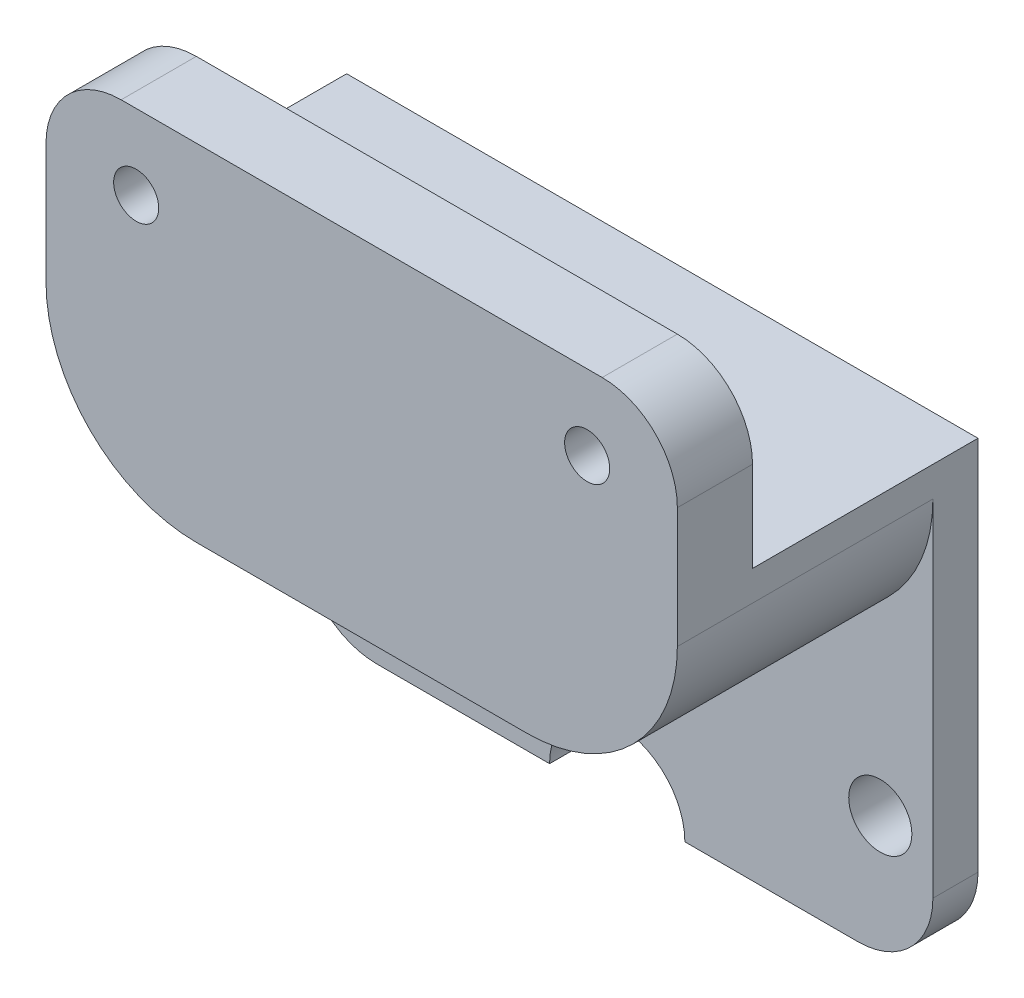
SolidWorks part; units mm, degrees
ref_plane "Front Plane" through (0, 0, 0) normal (0, 0, 1) x (1, 0, 0)
ref_plane "Top Plane" through (0, 0, 0) normal (0, 1, 0) x (1, 0, 0)
ref_plane "Right Plane" through (0, 0, 0) normal (1, 0, 0) x (0, 0, -1)
sketch "Sketch3" plane through (0, 0, 0) normal (0, 0, 1) x (1, 0, 0)
  line L0 (-22.5928, 16.5094) -> (-6.0928, 16.5094)
  line L1 (-48.0928, 16.5094) -> (-31.5928, 16.5094)
  line L2 (-48.0928, 16.5094) -> (-48.0928, 3.5094)
  line L3 (-38.0928, -6.4906) -> (-16.0928, -6.4906)
  line L4 (-6.0928, 16.5094) -> (-6.0928, 3.5094)
  line L5 (-31.5928, 16.5094) -> (-22.5928, 16.5094)
  circle A1 centre (-42.0928, 11.5094) radius 1.5
  circle A2 centre (-12.0928, 11.5094) radius 1.5
  arc A3 (-48.0928, 3.5094) -> (-38.0928, -6.4906) centre (-38.0928, 3.5094) ccw
  arc A4 (-16.0928, -6.4906) -> (-6.0928, 3.5094) centre (-16.0928, 3.5094) ccw
  point P12 (-27.0928, -6.4906)
  point P16 (-48.0928, -6.4906)
  dimension "D4" = 3
  dimension "D5" = 3
  dimension "D12" = 10
  dimension "D13" = 10
  dimension "D1" = 42
  dimension "D2" = 23
  dimension "D6" = 18
  dimension "D7" = 30
  dimension "D8" = 18
  dimension "D9" = 15
  dimension "D10" = 15
extrude "Boss-Extrude3" add sketch "Sketch3" along normal blind 5
sketch "Sketch6" plane through (0, 0, 0) normal (0, 0, 1) x (1, 0, 0)
  line L2 (-48.0928, 5.5094) -> (-48.0928, 3.5094)
  line L3 (-38.0928, -6.4906) -> (-16.0928, -6.4906)
  line L4 (-6.0928, 5.5094) -> (-6.0928, 3.5094)
  line L5 (-6.0928, 5.5094) -> (-48.0928, 5.5094)
  arc A3 (-48.0928, 3.5094) -> (-38.0928, -6.4906) centre (-38.0928, 3.5094) ccw
  arc A4 (-16.0928, -6.4906) -> (-6.0928, 3.5094) centre (-16.0928, 3.5094) ccw
  dimension "D1" = 12
extrude "Boss-Extrude4" add sketch "Sketch6" against normal blind 15
ref_plane "Plane7" through (0, 5.5094, 0) normal (0, 1, 0) x (1, 0, 0)
sketch "Sketch9" plane through (0, 5.5094, 0) normal (0, 1, 0) x (1, 0, 0)
  line L0 (-48.0928, 15) -> (-48.0928, 0) construction
  line L1 (-6.0928, 15) -> (-48.0928, 15)
  line L2 (-6.0928, 15) -> (-6.0928, 12)
  line L3 (-6.0928, 12) -> (-48.0928, 12)
  line L4 (-48.0928, 15) -> (-48.0928, 12)
  dimension "D1" = 42
  dimension "D2" = 3
fillet "Fillet4" radius 5 2 edges at (-48.0928, 16.5094, 2.5) (-6.0928, 16.5094, 2.5)
extrude "Boss-Extrude7" add sketch "Sketch9" against normal blind 30
fillet "Fillet6" radius 5 1 edges at (-6.0928, -24.4906, -13.5)
fillet "Fillet7" radius 5 1 edges at (-48.0928, -24.4906, -13.5)
ref_plane "Plane13" through (0, 0, -15) normal (0, 0, -1) x (-1, 0, 0)
sketch "Sketch11" plane through (0, 0, -15) normal (0, 0, -1) x (-1, 0, 0)
  line L0 (6.0928, -19.4906) -> (6.0928, 5.5094) construction
  line L3 (22.5928, -24.4906) -> (31.5928, -24.4906)
  line L4 (48.0928, 5.5094) -> (48.0928, -19.4906) construction
  arc A0 (31.5928, -24.4906) -> (22.5928, -24.4906) centre (27.0928, -24.4906) ccw
  circle A1 centre (9.5928, -16.4906) radius 2.1
  circle A2 centre (44.5928, -16.4906) radius 2.1
  dimension "D4" = 8
  dimension "D1" = 4.2
  dimension "D2" = 35
  dimension "D3" = 17.5
  dimension "D5" = 8
  dimension "D6" = 17.5
  dimension "D7" = 21
  dimension "D8" = 21
  dimension "D9" = 3.5
  dimension "D10" = 3.5
extrude "Cut-Extrude2" cut sketch "Sketch11" against normal blind 30
